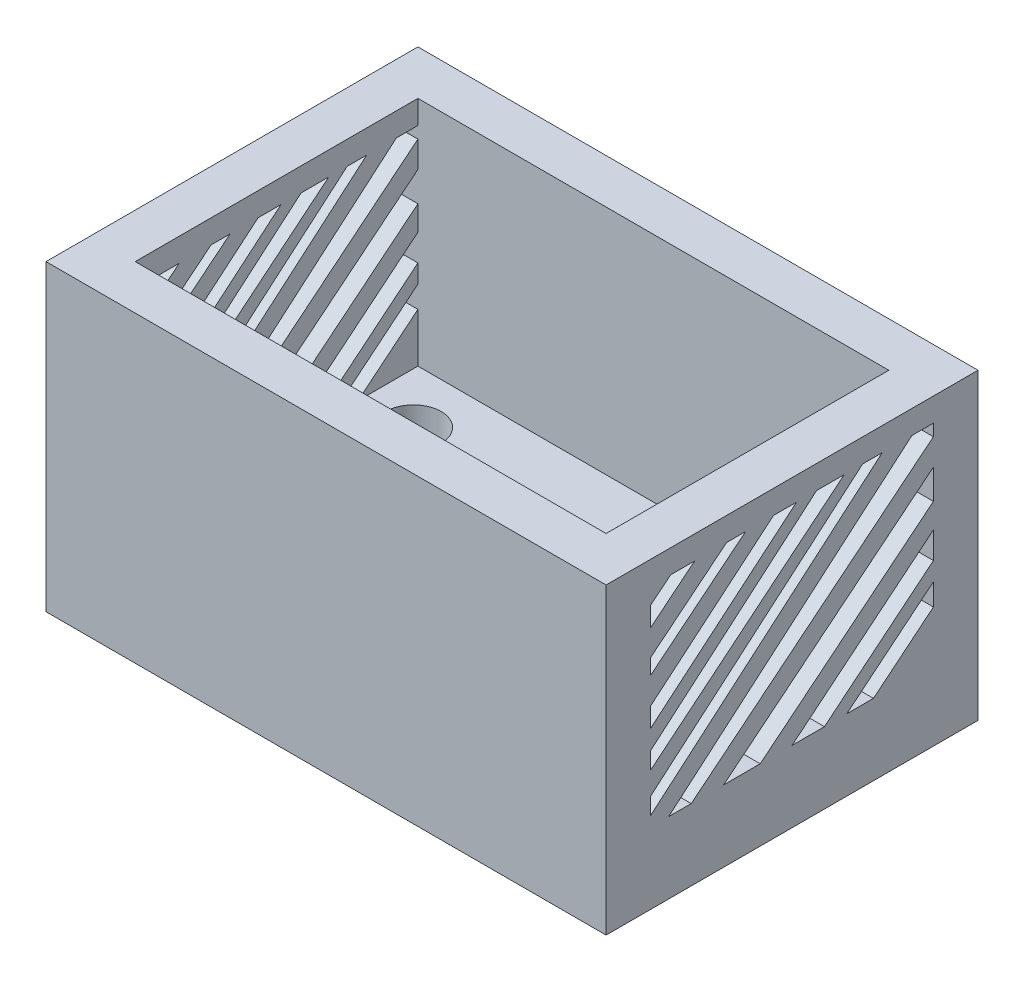
SolidWorks part; units mm, degrees
ref_plane "Front Plane" through (0, 0, 0) normal (0, 0, 1) x (1, 0, 0)
ref_plane "Top Plane" through (0, 0, 0) normal (0, 1, 0) x (1, 0, 0)
ref_plane "Right Plane" through (0, 0, 0) normal (1, 0, 0) x (0, 0, -1)
sketch "Sketch1" plane through (0, 0, 0) normal (0, 1, 0) x (1, 0, 0)
  line L1 (-15.7, 10.425) -> (15.7, 10.425)
  line L2 (-15.7, 10.425) -> (-15.7, -10.425)
  line L3 (-15.7, -10.425) -> (15.7, -10.425)
  line L4 (15.7, 10.425) -> (15.7, -10.425)
  line L5 (-15.7, 10.425) -> (15.7, -10.425) construction
  line L6 (-15.7, -10.425) -> (15.7, 10.425) construction
  line L7 (-13.2, 7.925) -> (13.2, 7.925)
  line L8 (-13.2, 7.925) -> (-13.2, -7.925)
  line L9 (-13.2, -7.925) -> (13.2, -7.925)
  line L10 (13.2, 7.925) -> (13.2, -7.925)
  line L11 (-13.2, 7.925) -> (13.2, -7.925) construction
  line L12 (-13.2, -7.925) -> (13.2, 7.925) construction
  point P0 (0, 0)
  point P6 (0, 0)
  dimension "D1" = 26.4
  dimension "D2" = 15.85
  dimension "D3" = 2.5
  dimension "D4" = 2.5
extrude "Boss-Extrude1" add sketch "Sketch1" along normal blind 4 contours L10 L7 L8 L9 | L4 L1 L2 L3 L7 L10 L9 L8 | L8 L7 L10 L9 | L2 L1 L4 L3 region at (0, 0, -10.0481) region at (0, 0, 0)
extrude "Boss-Extrude2" add sketch "Sketch1<3>" along normal blind 13 from surface starting at face at (0, 4, 0)
sketch "Sketch1<3>" plane through (0, 0, 0) normal (0, 1, 0) x (1, 0, 0) same geometry as "Sketch1"
sketch "Sketch2" plane through (0, 4, 0) normal (0, 1, 0) x (1, 0, 0)
  line L0 (13.2, 7.925) -> (13.2, -7.925) construction
  line L1 (-13.2, -7.925) -> (13.2, -7.925)
  line L2 (-13.2, -7.925) -> (-13.2, -4.725)
  line L3 (-13.2, -4.725) -> (13.2, -4.725)
  line L4 (13.2, -7.925) -> (13.2, -4.725)
  dimension "D1" = 3.2
extrude "Cut-Extrude1" cut sketch "Sketch2" against normal blind 2.7
sketch "Sketch3" plane through (15.7, 0, 0) normal (1, 0, 0) x (0, 0, -1)
  line L0 (-5.6517, 4) -> (-6.9195, 4)
  line L1 (-7.925, 14.774) -> (-6.8043, 15.683)
  line L3 (-5.4599, 15.683) -> (-7.925, 13.6836)
  line L4 (-7.925, 13.6836) -> (-7.925, 14.774)
  line L5 (-7.925, 12.2328) -> (-3.6712, 15.683)
  line L6 (-7.925, 17) -> (-7.925, 1.3)
  line L7 (-7.925, 1.3) -> (-4.725, 1.3)
  line L8 (-4.725, 1.3) -> (-4.725, 4)
  line L9 (-4.725, 4) -> (7.925, 4)
  line L10 (7.925, 4) -> (7.925, 17)
  line L11 (7.925, 17) -> (-7.925, 17)
  line L12 (-7.925, 14.774) -> (-7.925, 13.6836)
  line L15 (-3.8361, 4) -> (-1.7861, 4)
  line L16 (7.925, 6.7554) -> (7.925, 7.9825)
  line L19 (-2.6066, 15.683) -> (-7.925, 11.3693)
  line L20 (-7.925, 11.3693) -> (-7.925, 12.2328)
  line L21 (-7.925, 9.8832) -> (-1.0378, 15.683)
  line L23 (0.2517, 15.683) -> (-7.925, 8.7973)
  line L24 (-7.925, 8.7973) -> (-7.925, 9.8832)
  line L25 (-7.925, 7.7149) -> (1.3754, 15.683)
  line L27 (2.9271, 15.683) -> (-7.925, 6.767)
  line L28 (-7.925, 6.767) -> (-7.925, 7.7149)
  line L29 (-7.925, 5.5035) -> (3.9565, 15.683)
  line L31 (5.0545, 15.683) -> (-7.925, 4.5628)
  line L32 (-7.925, 4.5628) -> (-7.925, 5.5035)
  line L33 (-6.9195, 4) -> (6.7169, 15.683)
  line L34 (7.925, 15.683) -> (7.925, 15.0216)
  line L35 (7.925, 15.0216) -> (-5.6517, 4)
  line L36 (-5.6517, 4) -> (-6.9195, 4)
  line L37 (-3.8361, 4) -> (7.925, 13.5477)
  line L38 (7.925, 13.5477) -> (7.925, 11.8835)
  line L39 (7.925, 11.8835) -> (-1.7861, 4)
  line L40 (-1.7861, 4) -> (-3.8361, 4)
  line L41 (0, 4) -> (7.925, 10.5)
  line L42 (7.925, 10.5) -> (7.925, 9.0108)
  line L43 (7.925, 9.0108) -> (1.8157, 4)
  line L44 (1.8157, 4) -> (0, 4)
  line L45 (3.0694, 4) -> (7.925, 7.9825)
  line L46 (7.925, 7.9825) -> (7.925, 6.7554)
  line L47 (7.925, 6.7554) -> (4.5655, 4)
  line L48 (4.5655, 4) -> (3.0694, 4)
  line L49 (-6.8043, 15.683) -> (-5.4599, 15.683)
  line L52 (7.925, 15.0216) -> (7.925, 15.683)
  line L53 (7.925, 11.8835) -> (7.925, 13.5477)
  line L54 (7.925, 9.0108) -> (7.925, 10.5)
  line L55 (3.0694, 4) -> (4.5655, 4)
  line L56 (0, 4) -> (1.8157, 4)
  line L57 (-7.925, 5.5035) -> (-7.925, 4.5628)
  line L58 (-7.925, 7.7149) -> (-7.925, 6.767)
  line L59 (-7.925, 9.8832) -> (-7.925, 8.7973)
  line L60 (-7.925, 12.2328) -> (-7.925, 11.3693)
  line L61 (-3.6712, 15.683) -> (-2.6066, 15.683)
  line L62 (-1.0378, 15.683) -> (0.2517, 15.683)
  line L63 (1.3754, 15.683) -> (2.9271, 15.683)
  line L64 (3.9565, 15.683) -> (5.0545, 15.683)
  line L65 (6.7169, 15.683) -> (7.925, 15.683)
  dimension "D1" = 0
extrude "Cut-Extrude3" cut sketch "Sketch3" against normal blind 47.7 contours L49 L1 L4 L3 | L61 L5 L20 L19 | L62 L21 L24 L23 | L63 L25 L28 L27 | L64 L29 L32 L31 | L65 L33 L0 L35 L34 | L39 L38 L37 L15 | L44 L43 L42 L41 | L48 L47 L16 L45 region at (15.7, 10.2147, -1.1586) region at (15.7, 8.371, -2.5406) region at (15.7, 6.8938, -4.3968) region at (15.7, 14.9218, 6.9865) region at (15.7, 5.7031, -5.8485) region at (15.7, 10.3546, 1.7057) region at (15.7, 13.734, 5.5221) region at (15.7, 11.6773, 2.6154) region at (15.7, 12.5038, 4.1498)
hole_wizard "Ø1.0mm Dowel Hole1" positions "Sketch4" profile "Sketch5" hole size "Ø1.0" standard "ANSI Metric"
sketch "Sketch4" plane through (0, 4, 0) normal (0, 1, 0) x (1, 0, 0)
  line L0 (-13.2, 7.925) -> (13.2, 7.925) construction
  line L1 (-13.2, 4.5655) -> (-13.2, 7.925) construction
  line L2 (13.2, 7.925) -> (13.2, -7.925) construction
  point P0 (-10.35, 4.825)
  point P2 (10.35, 4.825)
  dimension "D1" = 3.1
  dimension "D2" = 3.1
  dimension "D3" = 2.85
  dimension "D4" = 2.85
sketch "Sketch5" plane through (-10.35, 4, -4.825) normal (1, 0, 0) x (0, 0, 1)
  line L0 (0, 0) -> (0, 55)
  line L1 (0, 55) -> (1.55, 54.0687)
  line L2 (1.55, 54.0687) -> (1.55, 0)
  line L5 (1.55, 0) -> (0, 0)
  line L10 (0, 55) -> (-1.55, 54.0687) construction
  line L11 (0, -6.35) -> (0, 107.95) construction
  dimension "Hole Dia." = 3.1
  dimension "Hole Depth" = 55
  dimension "Drill Angle" = 118
